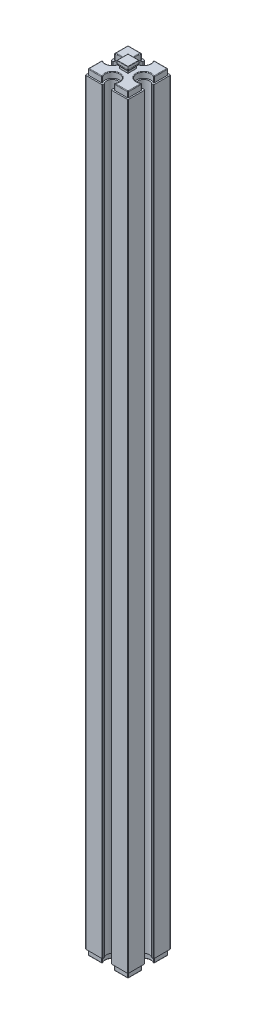
SolidWorks part; units mm, degrees
ref_plane "前视基准面" through (0, 0, 0) normal (0, 0, 1) x (1, 0, 0)
ref_plane "上视基准面" through (0, 0, 0) normal (0, 1, 0) x (1, 0, 0)
ref_plane "右视基准面" through (0, 0, 0) normal (1, 0, 0) x (0, 0, -1)
sketch "草图1" plane through (0, 0, 0) normal (0, 1, 0) x (1, 0, 0)
  line L0 (0, 0) -> (0, 7.5) construction
  line L1 (0, 0) -> (7.5, 0) construction
  line L2 (-7.5, 7.5) -> (-1.5, 7.5)
  line L3 (7.5, 7.5) -> (7.5, 1.5)
  line L4 (6.8229, 1.5) -> (7.5, 1.5)
  line L5 (6.8229, -1.5) -> (7.5, -1.5)
  line L6 (0, 7.5) -> (0, 5.5) construction
  line L7 (-1.5, 6.8229) -> (-1.5, 7.5)
  line L8 (1.5, 6.8229) -> (1.5, 7.5)
  line L9 (1.5, 7.5) -> (7.5, 7.5)
  line L10 (7.5, -1.5) -> (7.5, -7.5)
  line L11 (7.5, -7.5) -> (1.5, -7.5)
  line L12 (1.5, -6.8229) -> (1.5, -7.5)
  line L13 (-1.5, -6.8229) -> (-1.5, -7.5)
  line L14 (-1.5, -7.5) -> (-7.5, -7.5)
  line L15 (-7.5, -7.5) -> (-7.5, -1.5)
  line L16 (-6.8229, -1.5) -> (-7.5, -1.5)
  line L17 (-6.8229, 1.5) -> (-7.5, 1.5)
  line L18 (-7.5, 1.5) -> (-7.5, 7.5)
  arc A0 (-1.5, 6.8229) -> (1.5, 6.8229) centre (0, 5.5) ccw
  arc A1 (6.8229, 1.5) -> (6.8229, -1.5) centre (5.5, 0) ccw
  arc A2 (1.5, -6.8229) -> (-1.5, -6.8229) centre (0, -5.5) ccw
  arc A3 (-6.8229, -1.5) -> (-6.8229, 1.5) centre (-5.5, 0) ccw
  point P36 (0, 0)
  dimension "D6" = 4
  dimension "D7" = 2
  dimension "D1" = 7.5
  dimension "D2" = 7.5
  dimension "D3" = 2
  dimension "D4" = 7.5
  dimension "D5" = 1.5
extrude "凸台-拉伸1" add sketch "草图1" along normal blind 133
sketch "草图2" plane through (0, 133, 0) normal (0, 1, 0) x (1, 0, 0)
  line L0 (-7, 7) -> (-7, 2)
  line L1 (-7, 2) -> (-7, 2)
  line L2 (-7, -2) -> (-7, -2)
  line L3 (-7, -2) -> (-7, -7)
  line L4 (-7, -7) -> (-2, -7)
  line L5 (-2, -7) -> (-2, -7)
  line L6 (2, -7) -> (2, -7)
  line L7 (2, -7) -> (7, -7)
  line L8 (7, -7) -> (7, -2)
  line L9 (7, -2) -> (7, -2)
  line L10 (7, 2) -> (7, 2)
  line L11 (7, 2) -> (7, 7)
  line L12 (7, 7) -> (2, 7)
  line L13 (2, 7) -> (2, 7)
  line L14 (-2, 7) -> (-2, 7)
  line L15 (-2, 7) -> (-7, 7)
  line L16 (-7.5, 7.5) -> (-7.5, 1.5)
  line L17 (-7.5, 1.5) -> (-6.8229, 1.5)
  line L18 (-6.8229, -1.5) -> (-7.5, -1.5)
  line L19 (-7.5, -1.5) -> (-7.5, -7.5)
  line L20 (-7.5, -7.5) -> (-1.5, -7.5)
  line L21 (-1.5, -7.5) -> (-1.5, -6.8229)
  line L22 (1.5, -6.8229) -> (1.5, -7.5)
  line L23 (1.5, -7.5) -> (7.5, -7.5)
  line L24 (7.5, -7.5) -> (7.5, -1.5)
  line L25 (7.5, -1.5) -> (6.8229, -1.5)
  line L26 (6.8229, 1.5) -> (7.5, 1.5)
  line L27 (7.5, 1.5) -> (7.5, 7.5)
  line L28 (7.5, 7.5) -> (1.5, 7.5)
  line L29 (1.5, 7.5) -> (1.5, 6.8229)
  line L30 (-1.5, 6.8229) -> (-1.5, 7.5)
  line L31 (-1.5, 7.5) -> (-7.5, 7.5)
  line L32 (-7.5, 7.5) -> (-7.5, 1.5) construction
  line L33 (-7.5, 1.5) -> (-6.8229, 1.5) construction
  line L34 (-6.8229, -1.5) -> (-7.5, -1.5) construction
  line L35 (-7.5, -1.5) -> (-7.5, -7.5) construction
  line L36 (-7.5, -7.5) -> (-1.5, -7.5) construction
  line L37 (-1.5, -7.5) -> (-1.5, -6.8229) construction
  line L38 (1.5, -6.8229) -> (1.5, -7.5) construction
  line L39 (1.5, -7.5) -> (7.5, -7.5) construction
  line L40 (7.5, -7.5) -> (7.5, -1.5) construction
  line L41 (7.5, -1.5) -> (6.8229, -1.5) construction
  line L42 (6.8229, 1.5) -> (7.5, 1.5) construction
  line L43 (7.5, 1.5) -> (7.5, 7.5) construction
  line L44 (7.5, 7.5) -> (1.5, 7.5) construction
  line L45 (1.5, 7.5) -> (1.5, 6.8229) construction
  line L46 (-1.5, 6.8229) -> (-1.5, 7.5) construction
  line L47 (-1.5, 7.5) -> (-7.5, 7.5) construction
  arc A0 (-7, -2) -> (-7, 2) centre (-5.5, 0) ccw
  arc A1 (2, -7) -> (-2, -7) centre (0, -5.5) ccw
  arc A2 (7, 2) -> (7, -2) centre (5.5, 0) ccw
  arc A3 (-2, 7) -> (2, 7) centre (0, 5.5) ccw
  arc A4 (-6.8229, -1.5) -> (-6.8229, 1.5) centre (-5.5, 0) ccw
  arc A5 (1.5, -6.8229) -> (-1.5, -6.8229) centre (0, -5.5) ccw
  arc A6 (6.8229, 1.5) -> (6.8229, -1.5) centre (5.5, 0) ccw
  arc A7 (-1.5, 6.8229) -> (1.5, 6.8229) centre (0, 5.5) ccw
  arc A8 (-6.8229, -1.5) -> (-6.8229, 1.5) centre (-5.5, 0) ccw construction
  arc A9 (1.5, -6.8229) -> (-1.5, -6.8229) centre (0, -5.5) ccw construction
  arc A10 (6.8229, 1.5) -> (6.8229, -1.5) centre (5.5, 0) ccw construction
  arc A11 (-1.5, 6.8229) -> (1.5, 6.8229) centre (0, 5.5) ccw construction
  dimension "D1" = 0
  dimension "D2" = 0.5
extrude "凸台-拉伸2" add sketch "草图2" along normal blind 2
sketch "草图3" plane through (0, 0, 0) normal (1, 0, 0) x (0, 0, -1)
  line L0 (0, 135) -> (0, 137) construction
  line L1 (2.5, 135) -> (-2.5, 135) construction
  line L2 (0, 137) -> (0, 137.5) construction
  line L3 (-1.5, 135) -> (1.5, 135)
  line L4 (1.5, 135) -> (1.5, 135.6771)
  line L5 (-1.95, 137.5) -> (1.95, 137.5)
  line L6 (1.95, 137.5) -> (1.95, 136.5556)
  line L7 (-1.5, 135) -> (-1.5, 135.6771)
  line L8 (-1.95, 137.5) -> (-1.95, 136.5556)
  arc A0 (-1.5, 135.6771) -> (-1.95, 136.5556) centre (0, 137) cw
  arc A1 (1.5, 135.6771) -> (1.95, 136.5556) centre (0, 137) ccw
  dimension "D5" = 2
  dimension "D1" = 2
  dimension "D2" = 0.5
  dimension "D3" = 1.5
  dimension "D4" = 1.95
extrude "凸台-拉伸3" add sketch "草图3" along normal blind 2 and the other way blind 2
sketch "草图4" plane through (0, 0, 0) normal (0, 0, 1) x (1, 0, 0)
  line L0 (0, 135) -> (0, 137) construction
  line L2 (-2, 135) -> (2, 135) construction
  line L3 (0, 137) -> (0, 137.5) construction
  line L4 (-2, 137.5) -> (2, 137.5) construction
  line L5 (1.95, 137.5) -> (2, 137.5)
  line L6 (-1.95, 137.5) -> (-1.95, 136.5556)
  line L9 (-1.5, 135) -> (-1.5, 135.6771)
  line L10 (1.5, 135) -> (1.5, 135.6771)
  line L11 (1.95, 137.5) -> (1.95, 136.5556)
  line L12 (1.5, 135) -> (2, 135)
  line L13 (-2, 137.5) -> (-1.95, 137.5)
  line L14 (-2, 137.5) -> (-2, 135)
  line L15 (-2, 135) -> (-1.5, 135)
  line L16 (2, 137.5) -> (2, 135)
  arc A0 (-1.95, 136.5556) -> (-1.5, 135.6771) centre (0, 137) ccw
  arc A1 (1.95, 136.5556) -> (1.5, 135.6771) centre (0, 137) cw
  dimension "D1" = 2
  dimension "D2" = 1.5
  dimension "D3" = 1.95
fillet "圆角3" radius 0.2 13 edges at (-1.5, 66.5, -7.5) (1.5, 66.5, -7.5) (7.5, 66.5, -7.5) (7.5, 66.5, -1.5) (7.5, 66.5, 1.5) (7.5, 66.5, 7.5) (-1.5, 66.5, 7.5) (1.5, 66.5, 7.5) (-6.8229, 66.5, -1.5) (-7.5, 66.5, 7.5) (-7.5, 66.5, 1.5) (-7.5, 66.5, -1.5) (-7.5, 66.5, -7.5)
extrude "切除-拉伸1" cut sketch "草图4" against normal blind 3 and the other way blind 3
fillet "圆角4" radius 0.2 24 edges at (0, 135, 3) (-3, 135, 0) (0, 135, -3) (3, 135, 0) (7, 134, 2) (7, 134, -2) (2, 134, -7) (-2, 134, -7) (-7, 134, 2) (-7, 134, -2) (2, 134, 7) (-2, 134, 7) (7, 134, 7) (4.5, 135, 7) (7, 135, 4.5) (7, 135, -4.5) (7, 134, -7) (4.5, 135, -7) (-4.5, 135, -7) (-7, 134, -7) (-7, 135, -4.5) (-4.5, 135, 7) (-7, 135, 4.5) (-7, 134, 7)
fillet "圆角5" radius 0.1 4 edges at (0, 137.5, -1.95) (1.95, 137.5, 0) (0, 137.5, 1.95) (-1.95, 137.5, 0)
mirror "镜向1" of "圆角5", "圆角4", "切除-拉伸1", "圆角3", "凸台-拉伸3", "凸台-拉伸2", "凸台-拉伸1"
